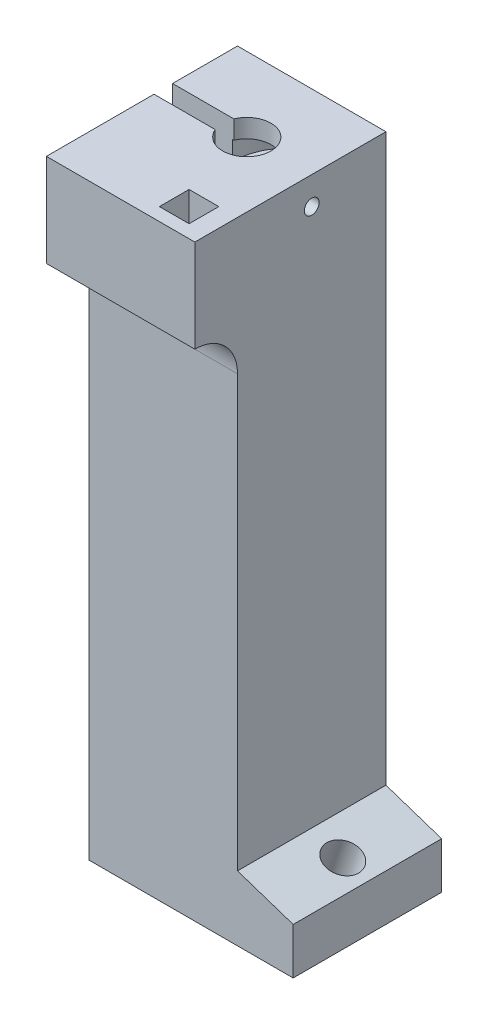
SolidWorks part; units mm, degrees
ref_plane "Front Plane" through (0, 0, 0) normal (0, 0, 1) x (1, 0, 0)
ref_plane "Top Plane" through (0, 0, 0) normal (0, 1, 0) x (1, 0, 0)
ref_plane "Right Plane" through (0, 0, 0) normal (1, 0, 0) x (0, 0, -1)
sketch "VerticalAxis" plane through (0, 0, 0) normal (0, 0, 1) x (1, 0, 0)
  line L0 (0, 0) -> (0, 42.951) construction
sketch "MainRotationalDesign" plane through (13.9419, 0, 0) normal (0, 0, -1) x (0, -1, 0)
  line L2 (5, 13.9419) -> (26.7642, 13.9419) construction
  line L3 (0, 13.9419) -> (-19.7322, 13.9419)
  line L4 (-7.75, 13.9419) -> (-7.75, 7.1919)
  point P0 (0, 13.9419)
  point P4 (0, 0)
  point P5 (0, 0)
  point P10 (0, 0)
  point P11 (0, 0)
  point P14 (5.666, 13.9419)
  dimension "D4" = 7.75
  dimension "D3" = 6.75
ref_plane "SingleChannelBasePlane" through (0, 7.75, 0) normal (0, 1, 0) x (0.9967, 0, 0.0811)
sketch "ShuttleOutline" plane through (-33.8949, 7.75, -2.7565) normal (0, 1, 0) x (0.9967, 0, 0.0811)
  line L0 (33.946, 0.7475) -> (38.9052, 1.4518) construction
  line L3 (39.0755, -0.6413) -> (34.0676, -0.7475) construction
  line L4 (36.4256, 1.0997) -> (36.9215, 1.1701)
  line L7 (36.9215, 1.1701) -> (36.9515, 0.8013)
  line L8 (36.4256, 1.0997) -> (33.9338, 0.897)
  line L9 (36.4256, 1.0997) -> (36.5715, -0.6944) construction
  line L10 (36.5715, -0.6944) -> (34.0797, -0.897)
  line L11 (33.9338, 0.897) -> (34.0797, -0.897) construction
  line L12 (36.9191, 1.2) -> (37.4175, 1.2405) construction
  line L13 (36.9191, 1.2) -> (36.9515, 0.8013) construction
  line L14 (36.9515, 0.8013) -> (37.4499, 0.8419)
  line L15 (37.4175, 1.2405) -> (37.4499, 0.8419)
  line L16 (37.5407, -0.2745) -> (37.0423, -0.315)
  line L17 (37.5407, -0.2745) -> (37.5731, -0.6731)
  line L18 (37.5731, -0.6731) -> (37.0747, -0.7137) construction
  line L19 (37.0423, -0.315) -> (37.0747, -0.7137) construction
  line L21 (36.5715, -0.6944) -> (37.0723, -0.6838)
  line L22 (37.0723, -0.6838) -> (37.0423, -0.315)
  line L23 (37.4175, 1.2405) -> (38.9052, 1.4518)
  line L24 (39.0755, -0.6413) -> (37.5731, -0.6731)
  line L25 (37.3414, 0.2712) -> (32.4051, -0.1303) construction
  line L26 (38.9052, 1.4518) -> (39.0755, -0.6413) construction
  line L27 (33.946, 0.7475) -> (34.0676, -0.7475) construction
  line L31 (34.0068, 0) -> (40.7346, 0.5471) construction
  circle A2 centre (38.9903, 0.4053) radius 0.6 construction
  circle A3 centre (38.9903, 0.4053) radius 0.4 construction
  circle A4 centre (34.0068, 0) radius 0.35 construction
  circle A5 centre (38.9903, 0.4053) radius 1.05 construction
  circle A6 centre (34.0068, 0) radius 0.75 construction
  arc A7 (33.9338, 0.897) -> (34.0797, -0.897) centre (34.0068, 0) ccw
  arc A8 (38.9052, 1.4518) -> (39.0755, -0.6413) centre (38.9903, 0.4053) cw
  point P4 (37.0723, -0.6838)
  point P15 (34.0068, 0)
  point P16 (36.9215, 1.1701)
  dimension "D2" = 1.2
  dimension "D3" = 0.8
  dimension "D4" = 0.7
  dimension "D1" = 1.5
  dimension "D5" = 2.1
  dimension "D6" = 5
  dimension "D10" = 1.8
  dimension "D9" = 2.5
  dimension "D11" = 2.5
  dimension "D12" = 0.5
  dimension "D14" = 1.5
  dimension "D7" = 0.4
sketch "ShuttleChannelOutline" plane through (33.8949, 7.75, 2.7565) normal (0, -1, 0) x (-0.9967, 0, -0.0811)
  line L0 (29.1854, 2.3987) -> (28.8611, -1.5881) construction
  line L1 (27.1169, -1.4463) -> (31.1037, -1.7705)
  line L2 (27.1169, -1.4463) -> (27.4411, 2.5405)
  line L3 (27.4411, 2.5405) -> (31.428, 2.2163)
  line L4 (31.1037, -1.7705) -> (31.428, 2.2163)
  line L5 (34.0068, 0) -> (27.279, 0.5471) construction
  line L6 (29.1084, 1.4518) -> (28.9381, -0.6413) construction
  line L8 (-199311.2371, 16211.4774) -> (199377.5178, -16211.3364) construction
  point P13 (27.279, 0.5471)
  point P16 (31.2658, 0.2229)
  dimension "D2" = 4
  dimension "D1" = 4
extrude "ShuttleChannelBody-Extrude" add sketch "ShuttleChannelOutline" against normal blind 15
sketch "Sketch23" plane through (0, 22.75, 0) normal (0, 1, 0) x (0.9959, 0, -0.09)
  line L0 (6.5427, -2.5991) -> (6.9025, 1.3847)
  line L1 (6.9025, 1.3847) -> (2.9188, 1.7445)
  line L2 (2.9188, 1.7445) -> (2.5589, -2.2393)
  line L3 (2.5589, -2.2393) -> (6.5427, -2.5991)
  line L4 (2.5589, -2.2393) -> (2.9188, 1.7445) construction
  circle A0 centre (4.9797, -0.4498) radius 0.425
  point P6 (0, 0)
  dimension "D1" = 0.85
extrude "ShuttleChannelCap-Extrude1" add sketch "Sketch23" along normal blind 1
sketch "Sketch22" plane through (0, 23.75, 0) normal (0, 1, 0) x (0.9909, 0, -0.1349)
  line L0 (6.4185, -2.8923) -> (2.4551, -2.3527)
  line L1 (2.4551, -2.3527) -> (2.9947, 1.6107)
  line L2 (2.9947, 1.6107) -> (6.9581, 1.0711)
  line L3 (6.9581, 1.0711) -> (6.4185, -2.8923)
  line L4 (5.0959, 0.3659) -> (4.8127, -1.7149) construction
  line L5 (0, 0) -> (6.6883, -0.9106) construction
  circle A0 centre (4.9543, -0.6745) radius 0.65 construction
  ellipse E0 centre (4.9543, -0.6745) end of major axis (5.1297, 0.6136) minor radius 0.65
  dimension "D1" = 1.3
  dimension "D2" = 2.6
extrude "ShuttleChannelCap-Extrude2" add sketch "Sketch22" along normal blind 0.5
sketch "Sketch24" plane through (0, 24.25, 0) normal (0, 1, 0) x (0.9909, 0, -0.1349)
  line L0 (6.4185, -2.8923) -> (6.9581, 1.0711)
  line L1 (6.9581, 1.0711) -> (2.9947, 1.6107)
  line L2 (2.9947, 1.6107) -> (2.4551, -2.3527)
  line L3 (2.4551, -2.3527) -> (6.4185, -2.8923)
  circle A0 centre (4.9543, -0.6745) radius 0.65
  circle A1 centre (4.9543, -0.6745) radius 0.65 construction
extrude "ShuttleChannelCap-Extrude3" add sketch "Sketch24" along normal blind 0.5
sketch "Sketch25" plane through (0, 24.75, 0) normal (0, 1, 0) x (0.9909, 0, -0.1349)
  line L2 (2.9947, 1.6107) -> (2.4551, -2.3527) construction
  line L4 (2.7586, -0.1233) -> (4.3935, -0.3458)
  line L5 (4.3935, -0.3458) -> (4.3261, -0.8413)
  line L6 (4.3261, -0.8413) -> (2.6911, -0.6187)
  line L7 (2.6911, -0.6187) -> (2.7586, -0.1233)
  circle A0 centre (4.9543, -0.6745) radius 0.65 construction
  point P2 (2.7249, -0.371)
  dimension "D1" = 0.5
extrude "ShuttleChannelCap-InjectionChannel" cut sketch "Sketch25" against normal up to surface (1 mm away) up to face at (4.575, 23.75, 0)
sketch "Sketch26" plane through (6.75, 0, 0) normal (-1, 0, 0) x (0, -0.8752, -0.4838)
  line L0 (-6.7828, -3.7491) -> (-21.0049, -11.6102) construction
  line L1 (-7.7503, -1.9987) -> (-5.8153, -5.4995) construction
  line L3 (-22.6288, -10.2226) -> (-20.6937, -13.7234) construction
  circle A0 centre (-21.0049, -11.6102) radius 0.2
  dimension "D1" = 0.4
  dimension "D2" = 0.75
extrude "ShuttleChannelCap-InjectionHole" cut sketch "Sketch26" along normal through all
fillet "ShuttleChannelCap-InjectionHole-Fillet" radius 0.25 1 edges at (5.6427, 23.9547, 0.1948)
extrude "Channel-Cut-Extrude12" cut sketch "ShuttleOutline" along normal blind 15 and the other way blind 5
fillet "Fillet1" radius 0.125 4 edges at (3, 15.25, 0.56) (3.5, 15.25, 0.56) (3.5, 15.25, -0.56) (3, 15.25, -0.56)
sketch "Sketch27" plane through (0, 0, 2) normal (0, 0, 1) x (1, 0, 0)
  line L0 (6.75, 7.75) -> (8.25, 7.75)
  line L1 (8.25, 7.75) -> (8.25, 9)
  line L2 (8.25, 9) -> (6.75, 9.5)
  line L3 (6.75, 24.75) -> (6.75, 7.75) construction
  line L4 (6.75, 9.5) -> (6.75, 7.75)
  dimension "D1" = 1.5
  dimension "D2" = 1.25
  dimension "D3" = 1.75
extrude "Boss-Extrude1" add sketch "Sketch27" against normal up to surface (4 mm away) up to face at (4.75, 16.25, -2)
sketch "Sketch28" plane through (3.525, 10.575, 0) normal (0.3162, 0.9487, 0) x (0.9487, -0.3162, 0)
  line L0 (4.9806, 0) -> (4.2806, 0) construction
  line L1 (4.9806, 2) -> (4.9806, -2) construction
  circle A0 centre (4.2806, 0) radius 0.45
  dimension "D1" = 0.9
  dimension "D2" = 0.7
extrude "Cut-Extrude1" cut sketch "Sketch28" against normal through all contours A0
sketch "Sketch29" plane through (0, 0, 2) normal (0, 0, 1) x (1, 0, 0)
  line L0 (2.75, 24.75) -> (2.75, 7.75) construction
  line L1 (6.75, 24.75) -> (2.75, 24.75)
  line L2 (6.75, 24.75) -> (6.75, 22.25)
  line L3 (6.75, 22.25) -> (2.75, 22.25)
  line L4 (2.75, 24.75) -> (2.75, 22.25)
  dimension "D1" = 2.5
extrude "Boss-Extrude2" add sketch "Sketch29" along normal blind 1.15
fillet "Fillet2" radius 1.15 1 edges at (4.75, 22.25, 2)
sketch "Sketch30" plane through (0, 24.75, 0) normal (0, 1, 0) x (1, 0, 0)
  line L0 (6.75, -2) -> (2.75, -2) construction
  line L1 (6.2452, -2.8) -> (5.4452, -2.8)
  line L2 (6.2452, -2.8) -> (6.2452, -2)
  line L3 (6.2452, -2) -> (5.4452, -2)
  line L4 (5.4452, -2.8) -> (5.4452, -2)
  dimension "D1" = 0.8
extrude "Cut-Extrude2" cut sketch "Sketch30" against normal blind 2
equation "\"DriveAngle\"= 37.5"
equation "\"WidthExtensionHalfOffset\"= 2.2mm"
equation "\"RotationMarginAngle\"= 17.5deg"
equation "\"Rotation\"= 180 - 2 * \"RotationMarginAngle\""
equation "\"DriveVerticalOffset\"= 5"
equation "\"ShuttleChannelBackWall\"= 1.75"
equation "\"ShuttleHoleSeparation\"=5"
equation "\"D6@ShuttleOutline\"=\"ShuttleHoleSeparation\""
equation "\"ElectrodePathToWall\"= \"ShuttleHoleSeparation\" + \"ShuttleChannelBackWall\""
equation "\"D3@MainRotationalDesign\"=\"ElectrodePathToWall\""
equation "\"ScrewHeadDiameter\"=1.3"
equation "\"D1@Sketch22\"=\"ScrewHeadDiameter\""
equation "\"D2@Sketch22\"=2*\"ScrewHeadDiameter\""
equation "\"ScrewFreeDiameter\"=0.85"
equation "\"D1@Sketch23\"=\"ScrewFreeDiameter\""
equation "\"ChannelWidth\"= 4"
equation "\"D2@ShuttleChannelOutline\"=\"ChannelWidth\""
equation "\"ChannelDepth\"=4"
equation "\"D1@ShuttleChannelOutline\"=\"ChannelDepth\""
equation "\"FullConnectedHeight\"=6"
equation "\"ActualOffset\"=7.75"
equation "\"D4@MainRotationalDesign\"=\"ActualOffset\""
equation "\"LooseTapDrill0_80\"=1.52"
equation "\"EIB_Mount_Screw_Head\"=2.54"
equation "\"TapDrill0_80\"=1.19"
equation "\"StimElectrodeBendAngle\"=24"
equation "\"ChannelTravel\"=15"
equation "\"D1@ShuttleChannelBody-Extrude\"=\"ChannelTravel\""
equation "\"StimChannelTravel\"= 15"
equation "\"StimChannelRotationOffset\"=20"
equation "\"D1\"= \"StimChannelTravel\""
equation "\"D1@Channel-Cut-Extrude12\" = \"ChannelTravel\""
